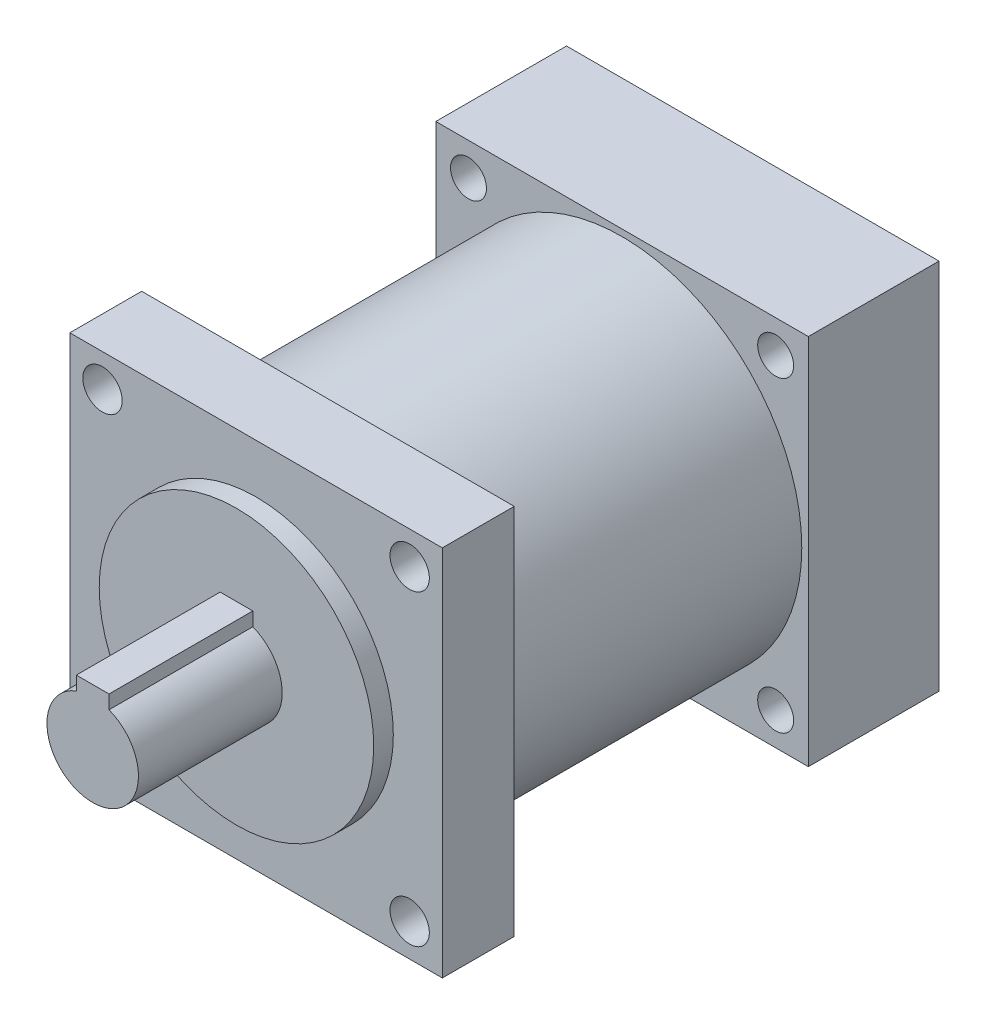
SolidWorks part; units mm, degrees
ref_plane "前视基准面" through (0, 0, 0) normal (0, 0, 1) x (1, 0, 0)
ref_plane "上视基准面" through (0, 0, 0) normal (0, 1, 0) x (1, 0, 0)
ref_plane "右视基准面" through (0, 0, 0) normal (1, 0, 0) x (0, 0, -1)
sketch "草图1" plane through (0, 0, 0) normal (0, 0, 1) x (1, 0, 0)
  line L0 (-23.5032, 11.7516) -> (33.4968, 11.7516) construction
  line L1 (-23.5032, 40.2516) -> (33.4968, 40.2516)
  line L2 (-23.5032, 40.2516) -> (-23.5032, -16.7484)
  line L3 (-23.5032, -16.7484) -> (33.4968, -16.7484)
  line L4 (33.4968, 40.2516) -> (33.4968, -16.7484)
  line L5 (4.9968, 40.2516) -> (4.9968, -16.7484) construction
  line L6 (-23.5032, 40.2516) -> (33.4968, -16.7484) construction
  circle A0 centre (-18.5032, 35.2516) radius 3.0101
  circle A1 centre (28.4968, 35.2516) radius 3.0101
  circle A2 centre (-18.5032, -11.7484) radius 3.0101
  circle A3 centre (28.4968, -11.7484) radius 3.0101
  dimension "D3" = 23.5
  dimension "D1" = 57
  dimension "D2" = 57
extrude "凸台-拉伸1" add sketch "草图1" along normal blind 11
sketch "草图2" plane through (0, 0, 11) normal (0, 0, 1) x (1, 0, 0)
  line L0 (-23.5032, 40.2516) -> (33.4968, -16.7484) construction
  line L1 (33.4968, 40.2516) -> (-23.5032, -16.7484) construction
  circle A0 centre (4.9968, 11.7516) radius 21
  dimension "D1" = 42
extrude "凸台-拉伸2" add sketch "草图2" along normal blind 3
sketch "草图3" plane through (0, 0, 14) normal (0, 0, 1) x (1, 0, 0)
  line L0 (4.9968, 32.7516) -> (4.9968, -9.2484) construction
  line L1 (7.4968, 20.39) -> (2.4968, 20.39)
  line L2 (2.4968, 20.39) -> (2.4968, 18.29)
  line L4 (7.4968, 20.39) -> (7.4968, 18.29)
  circle A0 centre (4.9968, 11.7516) radius 21 construction
  circle A1 centre (4.9968, 11.7516) radius 21 construction
  arc A2 (2.4968, 18.29) -> (7.4968, 18.29) centre (4.9968, 11.7516) ccw
  point P14 (4.9968, 18.29)
  point P15 (4.9968, 20.39)
  dimension "D1" = 14
  dimension "D2" = 2.5
  dimension "D3" = 2.1
extrude "凸台-拉伸3" add sketch "草图3" along normal blind 22
sketch "草图4" plane through (0, 0, 0) normal (0, 0, -1) x (-1, 0, 0)
  line L0 (-33.4968, 40.2516) -> (23.5032, -16.7484) construction
  line L1 (23.5032, 40.2516) -> (-33.4968, -16.7484) construction
  circle A0 centre (-4.9968, 11.7516) radius 27.5
  dimension "D1" = 55
extrude "凸台-拉伸4" add sketch "草图4" along normal blind 45
sketch "草图5" plane through (0, 0, -45) normal (0, 0, -1) x (-1, 0, 0)
  line L1 (-33.4968, -16.7484) -> (23.5032, -16.7484)
  line L2 (-33.4968, -16.7484) -> (-33.4968, 40.2516)
  line L3 (-33.4968, 40.2516) -> (23.5032, 40.2516)
  line L4 (23.5032, -16.7484) -> (23.5032, 40.2516)
  line L5 (-33.4968, -16.7484) -> (23.5032, 40.2516) construction
  line L6 (-33.4968, 40.2516) -> (23.5032, -16.7484) construction
  point P0 (-4.9968, 11.7516)
  dimension "D1" = 57
  dimension "D2" = 57
extrude "凸台-拉伸5" add sketch "草图5" along normal blind 20
sketch "草图6" plane through (0, 0, -65) normal (0, 0, -1) x (-1, 0, 0)
  line L0 (-33.4968, 40.2516) -> (23.5032, -16.7484) construction
  line L1 (23.5032, 40.2516) -> (-33.4968, -16.7484) construction
  line L2 (-4.9968, 40.2516) -> (-4.9968, -16.7484) construction
  line L3 (23.5032, 40.2516) -> (-33.4968, 40.2516) construction
  line L4 (-33.4968, -16.7484) -> (23.5032, -16.7484) construction
  circle A0 centre (-28.4968, 35.2516) radius 2.75
  circle A1 centre (18.5032, 35.2516) radius 2.75
  circle A2 centre (18.5032, -11.7484) radius 2.75
  circle A3 centre (-28.4968, -11.7484) radius 2.75
  dimension "D1" = 5.5
  dimension "D2" = 23.5
extrude "切除-拉伸1" cut sketch "草图6" against normal through all
sketch "草图7" plane through (0, 0, -65) normal (0, 0, -1) x (-1, 0, 0)
  line L0 (-33.4968, 40.2516) -> (23.5032, -16.7484) construction
  circle A0 centre (-4.9968, 11.7516) radius 22.0114
  point P3 (-4.9968, 11.7516)
extrude "切除-拉伸2" cut sketch "草图7" against normal blind 30
